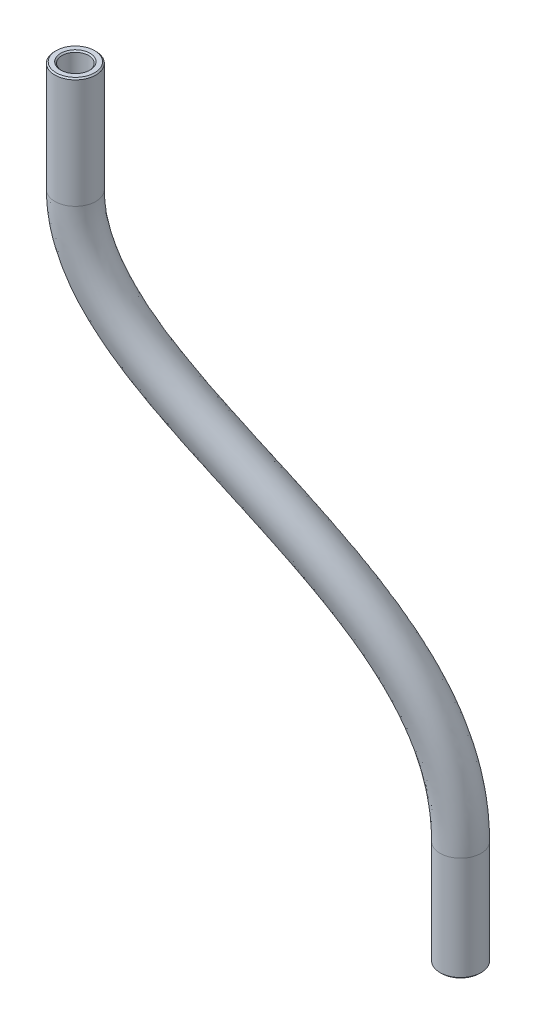
SolidWorks part; units mm, degrees
ref_plane "Front Plane" through (0, 0, 0) normal (0, 0, 1) x (1, 0, 0)
ref_plane "Top Plane" through (0, 0, 0) normal (0, 1, 0) x (1, 0, 0)
ref_plane "Right Plane" through (0, 0, 0) normal (1, 0, 0) x (0, 0, -1)
sketch3d "3DSketch1"
  line L0 (-150.0853, -93.2823, -17.525) -> (-150.0853, -103.4823, -17.525)
  line L1 (-177.2076, -35.8, -7.0986) -> (-177.2076, -46.6, -7.0986)
  spline S0 degree 3 poles (-177.2076, -46.6, -7.0986) (-177.2076, -53.9942, -7.0986) (-163.6464, -68.5471, -12.3118) (-150.0853, -81.2348, -17.525) (-150.0853, -93.2823, -17.525) knots 0 0 0 0 0.403418 1 1 1 1
sketch "Sketch1" plane through (0, -95.3823, 0) normal (0, 1, 0) x (1, 0, 0)
  circle A0 centre (-150.0853, 17.525) radius 2
  circle A1 centre (-150.0853, 17.525) radius 3.5 construction
  circle A2 centre (-150.0853, 17.525) radius 1.3
  dimension "D1" = 4
  dimension "D2" = 2.6
sweep "Sweep1" add profiles "Sketch1" path "3DSketch1"
chamfer "Chamfer1" distance 0.127 angle 45 4 edges at (-152.0853, -103.4823, -17.525) (-151.3853, -103.4823, -17.525) (-179.2076, -35.8, -7.0986) (-178.5076, -35.8, -7.0986)
